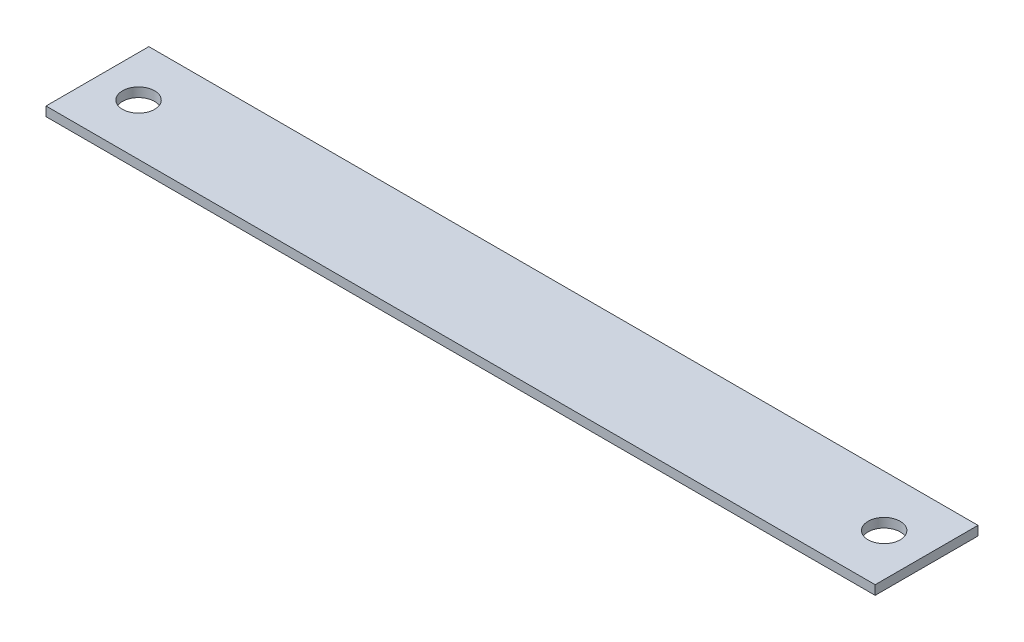
SolidWorks part; units mm, degrees
ref_plane "Front Plane" through (0, 0, 0) normal (0, 0, 1) x (1, 0, 0)
ref_plane "Top Plane" through (0, 0, 0) normal (0, 1, 0) x (1, 0, 0)
ref_plane "Right Plane" through (0, 0, 0) normal (1, 0, 0) x (0, 0, -1)
sketch "Sketch1" plane through (0, 0, 0) normal (0, 1, 0) x (1, 0, 0)
  line L1 (0, 0) -> (204.7875, 0)
  line L2 (0, 0) -> (0, 25.4)
  line L3 (0, 25.4) -> (204.7875, 25.4)
  line L4 (204.7875, 0) -> (204.7875, 25.4)
  dimension "D1" = 204.7875
  dimension "D2" = 25.4
extrude "Boss-Extrude1" add sketch "Sketch1" along normal blind 2.286
sketch "Sketch2" plane through (0, 2.286, 0) normal (0, 1, 0) x (1, 0, 0)
  line L0 (0, 25.4) -> (0, 0) construction
  circle A0 centre (10.16, 12.7) radius 3.9688
  circle A1 centre (194.31, 12.7) radius 3.9687
  point P8 (0, 12.7)
  dimension "D1" = 7.9375
  dimension "D2" = 184.15
  dimension "D3" = 10.16
  dimension "D4" = 7.9375
extrude "Cut-Extrude1" cut sketch "Sketch2" against normal through all
